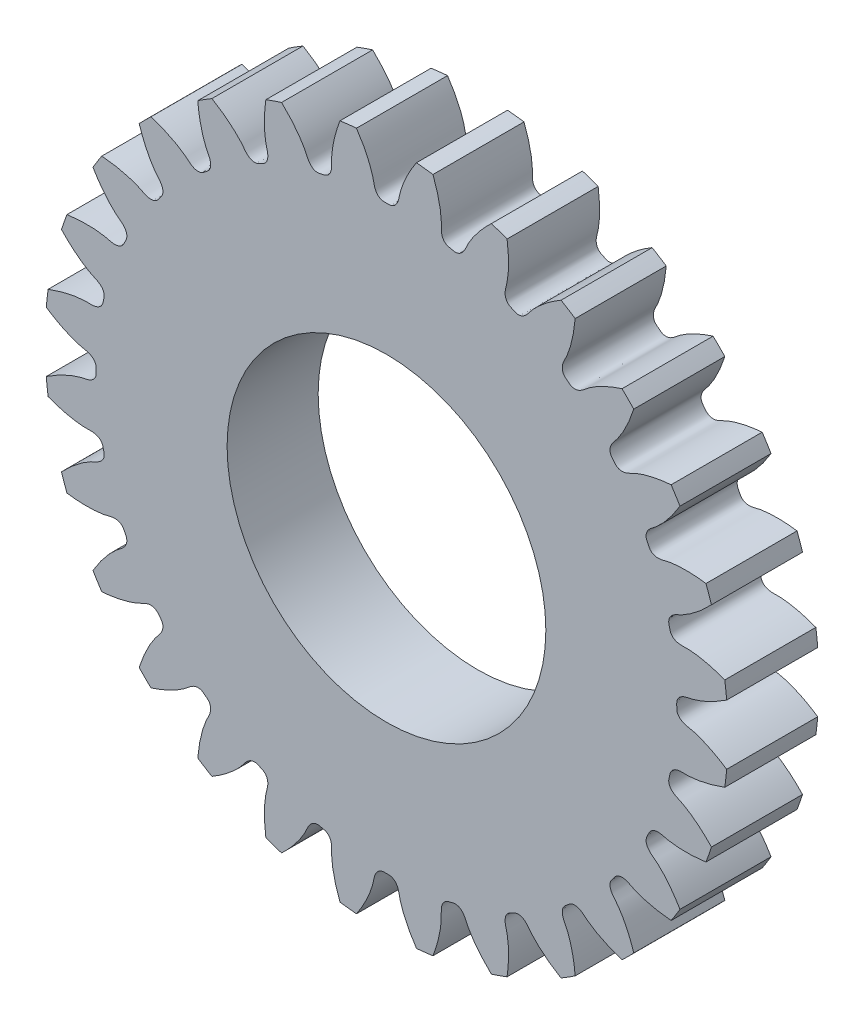
SolidWorks part; units mm, degrees
ref_plane "Front Plane" through (0, 0, 0) normal (0, 0, 1) x (1, 0, 0)
ref_plane "Top Plane" through (0, 0, 0) normal (0, 1, 0) x (1, 0, 0)
ref_plane "Right Plane" through (0, 0, 0) normal (1, 0, 0) x (0, 0, -1)
ref_axis "Axis1" through (0, 0, 55) along (0, 0, -1)
sketch "SketchRevolveSpurPinion" plane through (0, 0, 0) normal (1, 0, 0) x (0, 0, -1)
  line L0 (0, 0) -> (1, 0) construction
  line L1 (-2, 0) -> (-2, 15)
  line L2 (-2, 15) -> (2, 15)
  line L3 (2, 15) -> (2, 0)
  line L4 (2, 0) -> (-2, 0)
  dimension "Side1" = 2
  dimension "OutsideRadius" = 15
  dimension "Side2" = 2
revolve "SpurPinion" add sketch "SketchRevolveSpurPinion" angle 360 about L0
sketch "SketchToothSpurPinion" plane through (0, 0, 0) normal (0, 0, 1) x (1, 0, 0)
  arc A0 (14.9895, 1.3477) -> (14.9895, -1.3477) centre (0, 0) cw
  spline S0 degree 3 poles (14.9895, -1.3477) (14.8341, -1.2422) (14.6273, -1.1129) (14.3674, -0.9709) (14.2273, -0.8993) (14.0943, -0.836) (13.969, -0.7805) (13.8515, -0.7323) (13.7423, -0.6911) (13.6415, -0.6561) (13.5496, -0.6271) (13.4666, -0.6034) (13.3928, -0.5845) (13.2771, -0.5583) (13.1664, -0.541) (13.0647, -0.5056) (13.0146, -0.4844) (12.9658, -0.4588) (12.9179, -0.4274) (12.8704, -0.3877) (12.8245, -0.3364) (12.7835, -0.2698) (12.757, -0.1918) (12.7465, -0.0996) (12.752, 0) (12.7465, 0.0996) (12.757, 0.1918) (12.7835, 0.2698) (12.8245, 0.3364) (12.8704, 0.3877) (12.9179, 0.4274) (12.9658, 0.4588) (13.0146, 0.4844) (13.0647, 0.5056) (13.1664, 0.541) (13.2771, 0.5583) (13.3928, 0.5845) (13.4666, 0.6034) (13.5496, 0.6271) (13.6415, 0.6561) (13.7423, 0.6911) (13.8515, 0.7323) (13.969, 0.7805) (14.0943, 0.836) (14.2273, 0.8993) (14.3674, 0.9709) (14.6273, 1.1129) (14.8341, 1.2422) (14.9895, 1.3477) knots 0 0 0 0 0.101926 0.13223 0.160698 0.187329 0.212123 0.235081 0.256202 0.275487 0.292935 0.308546 0.322321 0.334259 0.372935 0.382829 0.392597 0.402447 0.412671 0.423662 0.43591 0.449896 0.465798 0.48017 0.5 0.51983 0.534202 0.550104 0.56409 0.576338 0.587329 0.597553 0.607403 0.617171 0.627065 0.665741 0.677679 0.691454 0.707065 0.724513 0.743798 0.764919 0.787877 0.812671 0.839302 0.86777 0.898074 1 1 1 1
extrude "ToothExtrudeCutSpurPinion" cut sketch "SketchToothSpurPinion" against normal blind 2 and the other way blind 2
pattern_circular "PatternSpurPinion" count 28 every 12.857 about axis through (0, 0, 55) along (0, 0, -1) of "ToothExtrudeCutSpurPinion"
sketch "BoreRevolveSketch" plane through (0, 0, 0) normal (1, 0, 0) x (0, 0, -1)
  line L0 (0, 0) -> (1, 0) construction
  line L1 (-2, 0) -> (2, 0)
  line L2 (2, 0) -> (2, 7)
  line L3 (2, 7) -> (-2, 7)
  line L4 (-2, 7) -> (-2, 0)
  dimension "BoreSide1" = 2
  dimension "TaperSide1" = 7
  dimension "BoreSide2" = 2
  dimension "TaperSide2" = 7
revolve "BoreRevolveCut" cut sketch "BoreRevolveSketch" angle 360 about L0
sketch "AuxiliarySketchSpurPinion" plane through (0, 0, 0) normal (0, 0, 1) x (1, 0, 0)
  circle A0 centre (0, 0) radius 14 construction
  circle A1 centre (0, 0) radius 13.1557 construction
  circle A2 centre (0, 0) radius 13.2665 construction
  circle A3 centre (0, 0) radius 15 construction
  circle A4 centre (0, 0) radius 12.75 construction
  dimension "PitchDiameter" = 28
  dimension "BaseDiameter" = 26.3114
  dimension "FormDiameter" = 26.5329
  dimension "MajorDiameter" = 30
  dimension "MinorDiameter" = 25.5
sketch "Sketch1" plane through (0, 0, 0) normal (0, 0, 1) x (1, 0, 0)
  circle A0 centre (0, 0) radius 7.1
  circle A1 centre (0, 0) radius 7 construction
  dimension "D1" = 0.1
extrude "Cut-Extrude1" [suppressed] cut sketch "Sketch1" against normal through all both and the other way through all
